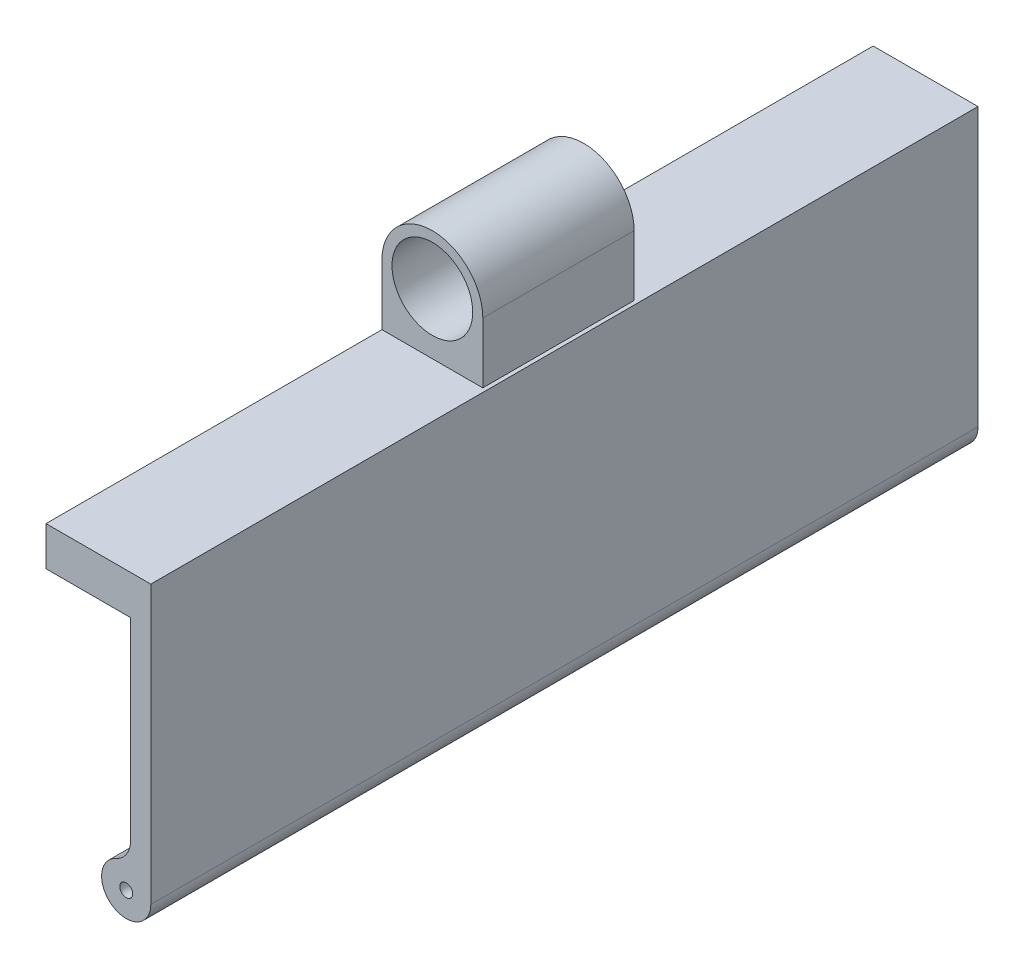
SolidWorks part; units mm, degrees
ref_plane "Front Plane" through (0, 0, 0) normal (0, 0, 1) x (1, 0, 0)
ref_plane "Top Plane" through (0, 0, 0) normal (0, 1, 0) x (1, 0, 0)
ref_plane "Right Plane" through (0, 0, 0) normal (1, 0, 0) x (0, 0, -1)
sketch "Sketch1" plane through (0, 0, 0) normal (0, 0, 1) x (1, 0, 0)
  line L0 (0, 0) -> (3.1723, 0) construction
  line L1 (2.44, 0) -> (2.44, 25)
  line L2 (0.44, 4.49) -> (0.44, 25)
  line L3 (0.44, 25) -> (2.44, 25)
  circle A0 centre (0, 0) radius 0.64
  arc A1 (-1.0175, 2.2177) -> (2.44, 0) centre (0, 0) ccw
  arc A2 (0.44, 4.49) -> (-1.0175, 2.2177) centre (-2.06, 4.49) cw
  dimension "D1" = 1.28
  dimension "D2" = 4.88
  dimension "D5" = 2.5
  dimension "D3" = 25
  dimension "D4" = 2
extrude "Boss-Extrude1" add sketch "Sketch1" along normal blind 82
sketch "Sketch3" plane through (0, 25, 0) normal (0, 1, 0) x (1, 0, 0)
  line L1 (0.44, -82) -> (2.44, -82)
  line L2 (0.44, -82) -> (0.44, 0)
  line L3 (0.44, 0) -> (2.44, 0)
  line L4 (2.44, -82) -> (2.44, 0)
extrude "Boss-Extrude4" add sketch "Sketch3" along normal blind 2.5
sketch "Sketch6" plane through (0.44, 0, 0) normal (-1, 0, 0) x (0, 0, 1)
  line L1 (82, 27.5) -> (0, 27.5)
  line L2 (82, 27.5) -> (82, 23.6193)
  line L3 (82, 23.6193) -> (0, 23.6193)
  line L4 (0, 27.5) -> (0, 23.6193)
  dimension "D1" = 23.01
extrude "Boss-Extrude5" add sketch "Sketch6" along normal blind 8.39
ref_plane "Plane2" through (-7.95, 23.6193, 0) normal (0, 0, 1) x (1, 0, 0)
ref_plane "Plane3" through (-7.95, 23.6193, 82) normal (0, 0, 1) x (1, 0, 0)
ref_plane "Plane4" through (0.44, 23.6193, 82) normal (0, 0, 1) x (1, 0, 0)
sketch "Sketch8" plane through (0, 0, 0) normal (0, 0, -1) x (-1, 0, 0)
  line L0 (7.95, 27.5) -> (7.95, 33.5)
  line L1 (-2.05, 33.5) -> (-2.05, 27.5)
  line L2 (-2.44, 27.5) -> (7.95, 27.5) construction
  line L3 (7.95, 27.5) -> (-2.05, 27.5)
  circle A0 centre (2.95, 33.5) radius 4
  arc A1 (7.95, 33.5) -> (-2.05, 33.5) centre (2.95, 33.5) ccw
  point P4 (0, 0)
extrude "Boss-Extrude6" add sketch "Sketch8" against normal blind 15 from offset 33.7 offset against normal yes
